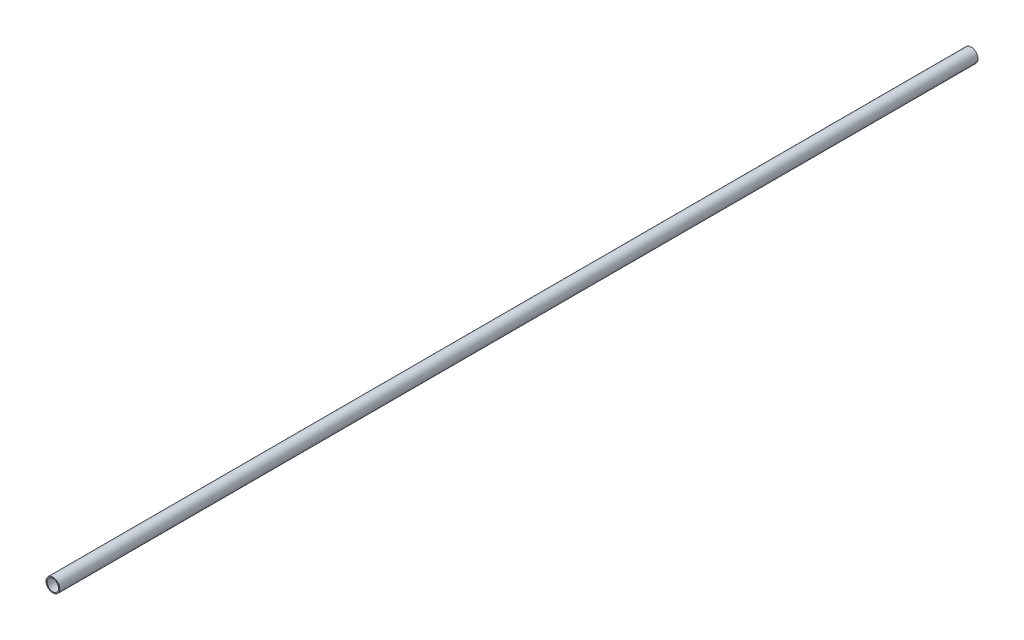
SolidWorks part; units mm, degrees
material "Thornel Mat VMA"
ref_plane "Front Plane" through (0, 0, 0) normal (0, 0, 1) x (1, 0, 0)
ref_plane "Top Plane" through (0, 0, 0) normal (0, 1, 0) x (1, 0, 0)
ref_plane "Right Plane" through (0, 0, 0) normal (1, 0, 0) x (0, 0, -1)
sketch "Sketch1" plane through (0, 0, 0) normal (0, 0, 1) x (1, 0, 0)
  circle A0 centre (0, 0) radius 3
  circle A1 centre (0, 0) radius 2.5
  dimension "D1" = 6
  dimension "D2" = 5
extrude "Boss-Extrude1" add sketch "Sketch1" along normal mid plane 400.05
